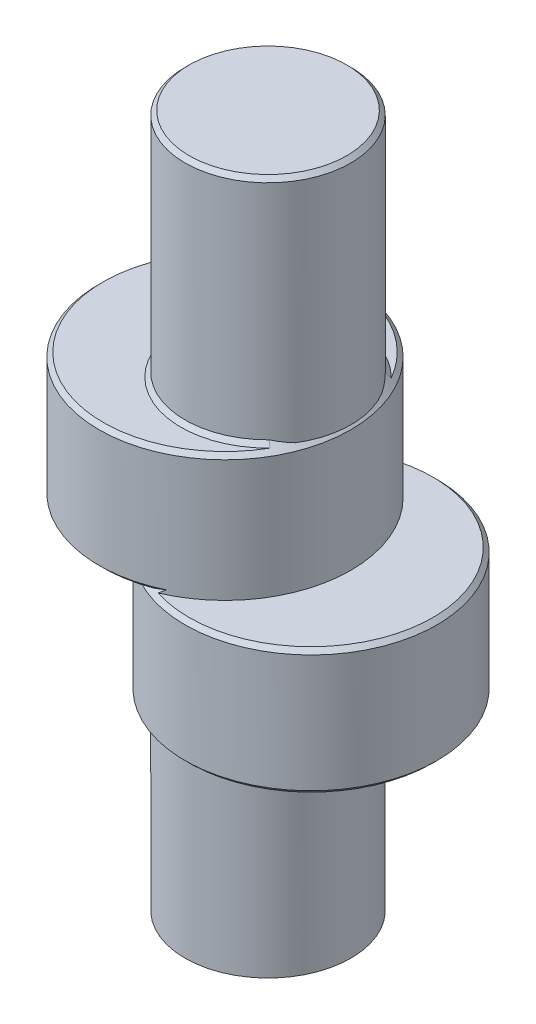
SolidWorks part; units mm, degrees
ref_plane "Plan de face" through (0, 0, 0) normal (0, 0, 1) x (1, 0, 0)
ref_plane "Plan de dessus" through (0, 0, 0) normal (0, 1, 0) x (1, 0, 0)
ref_plane "Plan de droite" through (0, 0, 0) normal (1, 0, 0) x (0, 0, -1)
sketch "Esquisse1" plane through (0, 0, 0) normal (0, 1, 0) x (1, 0, 0)
  line L0 (0, -3.175) -> (0, 2.825) construction
  circle A0 centre (0, 0) radius 3.95
  point P9 (0, 2.825)
  dimension "D1" = 7.9
  dimension "D3" = 6
extrude "Boss.-Extru.1" add sketch "Esquisse1" along normal blind 10
sketch "Esquisse2" plane through (0, 10, 0) normal (0, 1, 0) x (1, 0, 0)
  circle A0 centre (2.05, 0) radius 6
  circle A1 centre (0, 0) radius 3.95 construction
  dimension "D1" = 12
extrude "Boss.-Extru.2" add sketch "Esquisse2" along normal blind 6
chamfer "Chanfrein1" distance 0.2 angle 45 1 edges at (2.05, 16, 6)
sketch "Esquisse3" plane through (0, 16, 0) normal (0, 1, 0) x (1, 0, 0)
  circle A0 centre (-2.05, 0) radius 6
  circle A1 centre (0, 0) radius 3.95
  dimension "D1" = 7.9
  dimension "D2" = 12
extrude "Boss.-Extru.3" add sketch "Esquisse3" along normal blind 6 contours A0
chamfer "Chanfrein2" distance 0.2 angle 45 2 edges at (-2.05, 22, 6) (-8.05, 16, 0)
sketch "Esquisse4" plane through (0, 22, 0) normal (0, 1, 0) x (1, 0, 0)
  circle A0 centre (0, 0) radius 3.95
  dimension "D1" = 7.9
extrude "Boss.-Extru.4" add sketch "Esquisse4" along normal blind 11
chamfer "Chanfrein3" distance 0.2 angle 45 2 edges at (-3.95, 22, 0) (0, 33, 3.95)
sketch "Esquisse5" plane through (0, 0, 0) normal (0, -1, 0) x (1, 0, 0)
  line L0 (-1.3638, -2.95) -> (1.3638, -2.95)
  line L1 (0, -2.95) -> (0, 3.25) construction
  circle A0 centre (0, 0) radius 3.95
  arc A1 (1.3638, -2.95) -> (-1.3638, -2.95) centre (0, 0) ccw
  circle A2 centre (0, 0) radius 3.25
  dimension "D1" = 7.9
  dimension "D2" = 3.25
  dimension "D3" = 6.2
extrude "Boss.-Extru.5" add sketch "Esquisse5" against normal blind 10 contours A0 | A1 L0
chamfer "Chanfrein4" distance 0.2 angle 45 1 edges at (2.05, 10, 6)
sketch "Esquisse6" plane through (0, 0, 0) normal (0, -1, 0) x (1, 0, 0)
  line L0 (1.3638, -2.95) -> (-1.3638, -2.95)
  line L1 (0, -2.95) -> (0, 3.25) construction
  arc A0 (1.3638, -2.95) -> (-1.3638, -2.95) centre (0, 0) ccw
  dimension "D1" = 3.25
  dimension "D2" = 6.2
extrude "Enlèv. mat.-Extru.1" cut sketch "Esquisse6" against normal blind 14
